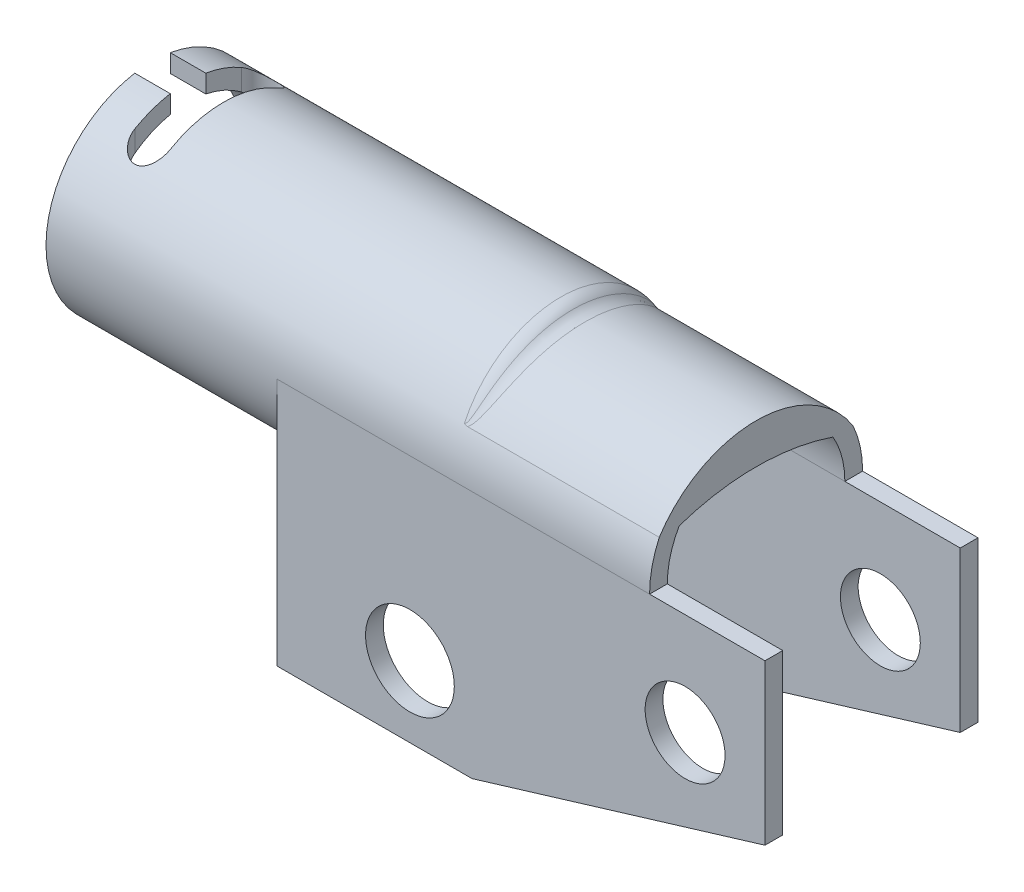
SolidWorks part; units mm, degrees
note: The reader was unsure of these and kept them because the rebuilt part matched: shared geometry of "Sketch2<3>".
ref_plane "Front Plane" through (0, 0, 0) normal (0, 0, 1) x (1, 0, 0)
ref_plane "Top Plane" through (0, 0, 0) normal (0, 1, 0) x (1, 0, 0)
ref_plane "Right Plane" through (0, 0, 0) normal (1, 0, 0) x (0, 0, -1)
sketch "Sketch1" plane through (0, 0, 0) normal (1, 0, 0) x (0, 0, -1)
  circle A0 centre (0, 0) radius 10
  dimension "D1" = 20
extrude "Extrude-Thin1" add sketch "Sketch1" against normal blind 48 thin
sketch "Sketch2" plane through (0, 0, 0) normal (0, 0, 1) x (1, 0, 0)
  line L0 (33, -18) -> (0, -28)
  line L1 (-22, 0) -> (33, 0)
  line L2 (-22, 0) -> (-22, -28)
  line L3 (-22, -28) -> (33, -28)
  line L4 (33, 0) -> (33, -28)
  line L5 (-48, 12) -> (-48, -12) construction
  circle A0 centre (-7, -20) radius 5
  circle A1 centre (24, -11.5) radius 4.5
  dimension "D8" = 10
  dimension "D9" = 9
  dimension "D1" = 55
  dimension "D2" = 28
  dimension "D3" = 26
  dimension "D4" = 33
  dimension "D5" = 10
  dimension "D6" = 40
  dimension "D7" = 8
  dimension "D10" = 9
  dimension "D11" = 11.5
extrude "Cut-Extrude1" cut sketch "Sketch2" against normal through all both and the other way through all contours L4 L1 L2 L3 L0 A1 A0
extrude "Boss-Extrude1" add sketch "Sketch2<3>" along normal blind 2 from offset 10 separate body contours L4 L1 L2 L3 L0 A1 A0
sketch "Sketch2<3>" plane through (0, 0, 0) normal (0, 0, 1) x (1, 0, 0) same geometry as "Sketch2"
mirror "Mirror2" about plane through (0, 0, 0) normal (0, 0, 1) of "Boss-Extrude1"
sketch "Sketch3" plane through (0, 0, 0) normal (1, 0, 0) x (0, 0, -1)
  line L0 (-12, 0) -> (-10, 0) construction
  line L1 (-12, 0) -> (-10, 0)
  line L2 (0, 0) -> (0, 4.494) construction
  line L3 (12, 0) -> (10, 0)
  arc A0 (-10.9087, 5) -> (10.9087, 5) centre (0, -2.0711) cw
  arc A1 (12, 0) -> (-12, 0) centre (0, 0) ccw construction
  arc A2 (-8.6603, 5) -> (8.6603, 5) centre (0, -20.5734) cw
  arc A3 (10, 0) -> (-10, 0) centre (0, 0) ccw construction
  arc A4 (-10.9087, 5) -> (-12, 0) centre (0, 0) ccw
  arc A5 (-8.6603, 5) -> (-10, 0) centre (0, 0) ccw
  arc A6 (10.9087, 5) -> (12, 0) centre (0, 0) cw
  arc A7 (8.6603, 5) -> (10, 0) centre (0, 0) cw
  dimension "D3" = 13
  dimension "D4" = 27
  dimension "D1" = 5
  dimension "D2" = 5
extrude "Boss-Extrude2" add sketch "Sketch3" along normal blind 20
fillet "Fillet1" radius 2 2 edges at (0, 10.9289, 0) (0, 12, 0)
fillet "Fillet2" radius 2 1 edges at (-0.2964, 10.2982, 4)
sketch "Sketch4" plane through (0, 0, 0) normal (0, 1, 0) x (1, 0, 0)
  line L0 (-48, 12) -> (-48, -12) construction
  line L1 (-48, -2) -> (-44, -2)
  line L2 (-48, -2) -> (-48, 2)
  line L3 (-48, 2) -> (-44, 2)
  line L4 (-44, -2) -> (-44, 2)
  line L5 (-42, 6) -> (-42, -6) construction
  line L6 (-40, 6) -> (-40, -6)
  line L7 (-44, 6) -> (-44, -6)
  line L8 (-48, 0) -> (-42, 0) construction
  arc A0 (-40, 6) -> (-44, 6) centre (-42, 6) ccw
  arc A1 (-44, -6) -> (-40, -6) centre (-42, -6) ccw
  point P8 (-42, 0)
  point P13 (-42, 4)
  point P14 (-44, 0)
  point P15 (-44, 0)
  dimension "D4" = 2
  dimension "D1" = 4
  dimension "D2" = 4
  dimension "D3" = 4
extrude "Cut-Extrude2" cut sketch "Sketch4" along normal through all contours L7 A1 L6 A0 L4 | L1 L4 L3 L2
